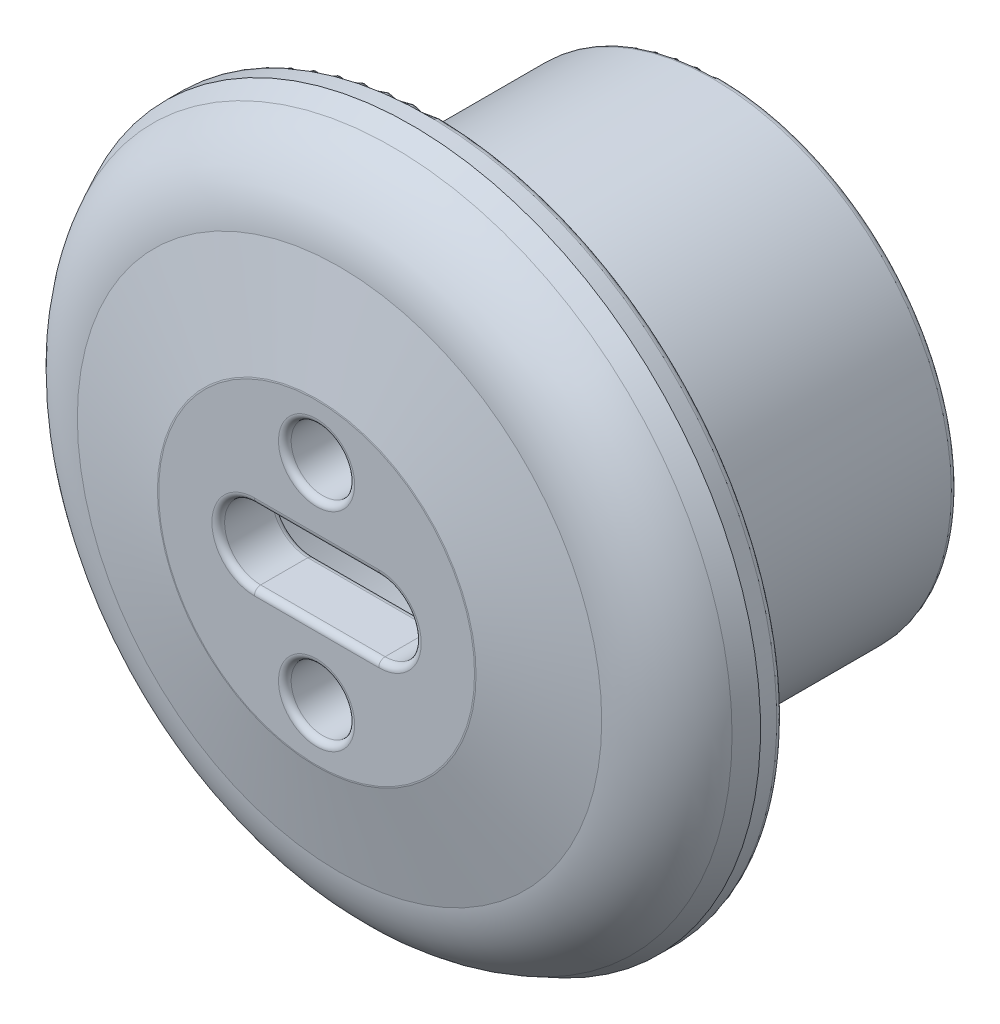
SolidWorks part; units mm, degrees
ref_plane "Front Plane" through (0, 0, 0) normal (0, 0, 1) x (1, 0, 0)
ref_plane "Top Plane" through (0, 0, 0) normal (0, 1, 0) x (1, 0, 0)
ref_plane "Right Plane" through (0, 0, 0) normal (1, 0, 0) x (0, 0, -1)
sketch "Sketch1" plane through (0, 0, 0) normal (1, 0, 0) x (0, 0, -1)
  line L0 (0, 0) -> (0, 10.99) construction
  line L1 (0, 10.99) -> (3, 10.99) construction
  line L3 (2.3972, 10.696) -> (3, 10.99)
  line L4 (3, 10.99) -> (3.7122, 10.99)
  line L5 (3.7122, 10.99) -> (3.7122, 8.99)
  line L6 (3.7122, 8.99) -> (4.7122, 8.99)
  line L7 (4.7122, 8.99) -> (4.7122, 7.49)
  line L8 (4.7122, 7.49) -> (12.7122, 7.49)
  line L11 (0, 0) -> (0, 5)
  line L12 (0, 5) -> (0.7238, 8.2626)
  line L13 (12.7122, 7.49) -> (12.7122, 6.49)
  line L14 (12.7122, 6.49) -> (3.2567, 6.49)
  line L18 (1.8825, 0) -> (0, 0)
  line L19 (3.2567, 6.49) -> (2.8825, 6.49)
  line L20 (1.8825, 5.49) -> (1.8825, 0)
  arc A0 (0.7238, 8.2626) -> (2.3972, 10.696) centre (3.7122, 7.9996) cw
  arc A1 (2.8825, 6.49) -> (1.8825, 5.49) centre (2.8825, 5.49) ccw
  dimension "D3" = 3
  dimension "D10" = 1
  dimension "D1" = 10.99
  dimension "D2" = 3
  dimension "D4" = 2
  dimension "D5" = 1
  dimension "D6" = 1.5
  dimension "D7" = 8
  dimension "D8" = 1
  dimension "D9" = 5
revolve "Revolve1" add sketch "Sketch1" angle 360 about L18
fillet "Fillet2" radius 0.2 4 edges at (-6.49, 0, -12.7122) (-10.99, 0, -3.7122) (-8.99, 0, -4.7122) (-7.49, 0, -12.7122)
sketch "Sketch2" plane through (0, 0, 0) normal (0, 0, 1) x (1, 0, 0)
  line L0 (-1.9596, 0) -> (1.9596, 0) construction
  line L1 (-1.9596, 1.1382) -> (1.9596, 1.1382)
  line L2 (-1.9596, -1.1382) -> (1.9596, -1.1382)
  line L3 (0, 0) -> (0, 3.2744) construction
  line L4 (0, 0) -> (6.2637, 0) construction
  line L5 (6.2637, 0) -> (-6.8437, 0) construction
  arc A0 (-1.9596, 1.1382) -> (-1.9596, -1.1382) centre (-1.9596, 0) ccw
  arc A1 (1.9596, -1.1382) -> (1.9596, 1.1382) centre (1.9596, 0) ccw
  circle A2 centre (0, 3.2744) radius 1
  circle A3 centre (0, -3.2744) radius 1
  point P2 (0, 0)
  dimension "D1" = 2
extrude "Cut-Extrude1" cut sketch "Sketch2" against normal blind 10
fillet "Fillet3" radius 0.2 13 edges at (0, 1.1382, -1.8825) (3.0978, 0, -1.8825) (0, -1.1382, -1.8825) (-3.0978, 0, -1.8825) (-1, 3.2744, -1.8825) (-1, -3.2744, -1.8825) (-5, 0, 0) (0, -1.1382, 0) (3.0978, 0, 0) (0, 1.1382, 0) (-3.0978, 0, 0) (1, 3.2744, 0) (-1, -3.2744, 0)
